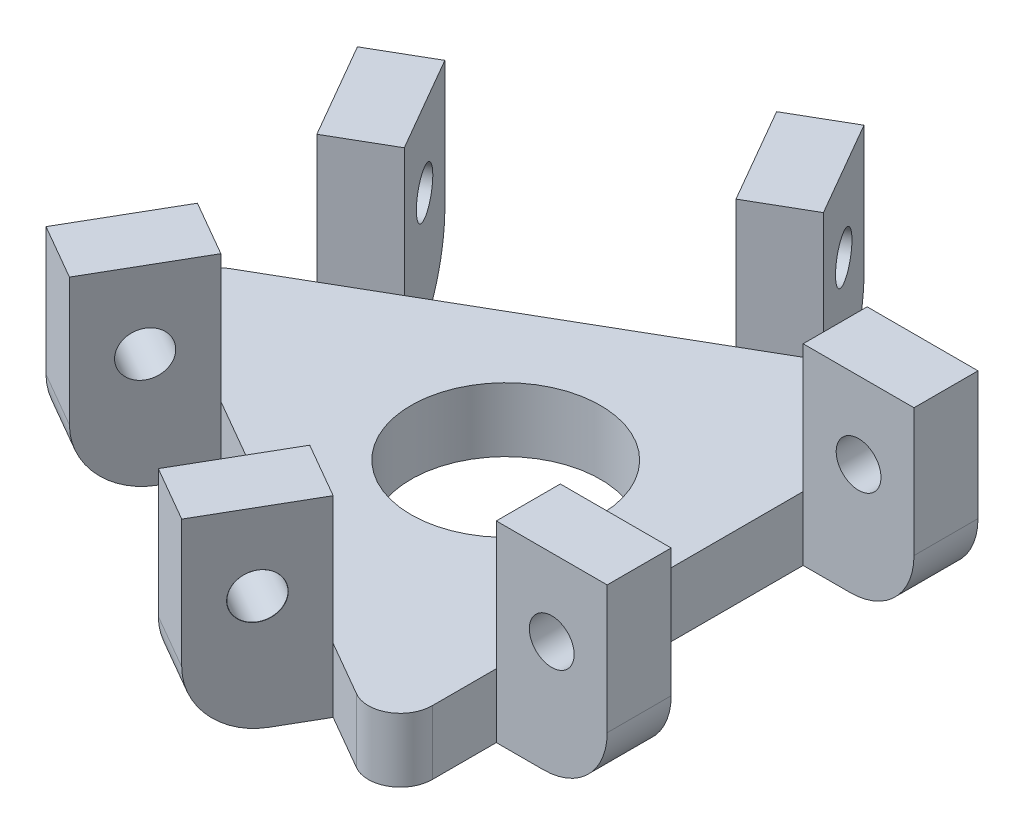
SolidWorks part; units mm, degrees
material "PLA"
ref_plane "Front" through (0, 0, 0) normal (0, 0, 1) x (1, 0, 0)
ref_plane "Top" through (0, 0, 0) normal (0, 1, 0) x (1, 0, 0)
ref_plane "Right" through (0, 0, 0) normal (1, 0, 0) x (0, 0, -1)
sketch "Sketch2" plane through (0, 0, 0) normal (0, 1, 0) x (0, 0, -1)
  line L0 (0, 0) -> (0, 50) construction
  line L1 (0, 0) -> (-43.3013, -25) construction
  line L2 (-43.3013, -20) -> (-38.3013, -11.3397)
  line L3 (4.3301, 47.5) -> (9.3301, 38.8397)
  line L4 (38.9711, -27.5) -> (28.9711, -27.5)
  line L5 (0, 0) -> (-23.8157, 13.75) construction
  line L9 (-38.3013, -11.3397) -> (-53.3013, -2.6795)
  line L10 (-33.3013, -2.6795) -> (-48.3013, 5.9808)
  line L11 (-53.3013, -2.6795) -> (-48.3013, 5.9808)
  line L12 (-14.3301, 30.1795) -> (-29.3301, 38.8397)
  line L13 (-24.3301, 47.5) -> (-29.3301, 38.8397)
  line L14 (-9.3301, 38.8397) -> (-24.3301, 47.5)
  line L17 (9.3301, 38.8397) -> (24.3301, 47.5)
  line L18 (24.3301, 47.5) -> (29.3301, 38.8397)
  line L19 (14.3301, 30.1795) -> (29.3301, 38.8397)
  line L20 (33.3013, -2.6795) -> (48.3013, 5.9808)
  line L21 (53.3013, -2.6795) -> (48.3013, 5.9808)
  line L22 (38.3013, -11.3397) -> (53.3013, -2.6795)
  line L25 (28.9711, -27.5) -> (28.9711, -44.8205)
  line L26 (28.9711, -44.8205) -> (18.9711, -44.8205)
  line L27 (18.9711, -27.5) -> (18.9711, -44.8205)
  line L28 (-28.9711, -27.5) -> (-28.9711, -44.8205)
  line L29 (-28.9711, -44.8205) -> (-18.9711, -44.8205)
  line L30 (-18.9711, -27.5) -> (-18.9711, -44.8205)
  line L32 (-33.3013, -2.6795) -> (-14.3301, 30.1795)
  line L33 (-9.3301, 38.8397) -> (-4.3301, 47.5)
  line L34 (14.3301, 30.1795) -> (33.3013, -2.6795)
  line L35 (38.3013, -11.3397) -> (43.3013, -20)
  line L36 (18.9711, -27.5) -> (-18.9711, -27.5)
  line L37 (-28.9711, -27.5) -> (-38.9711, -27.5)
  line L38 (-38.3013, -11.3397) -> (-33.3013, -2.6795)
  line L39 (-9.3301, 38.8397) -> (-14.3301, 30.1795)
  line L40 (9.3301, 38.8397) -> (14.3301, 30.1795)
  line L41 (38.3013, -11.3397) -> (33.3013, -2.6795)
  line L42 (28.9711, -27.5) -> (18.9711, -27.5)
  line L43 (-28.9711, -27.5) -> (-18.9711, -27.5)
  arc A0 (-43.3013, -20) -> (-38.9711, -27.5) centre (-38.9711, -22.5) ccw
  arc A1 (43.3013, -20) -> (38.9711, -27.5) centre (38.9711, -22.5) cw
  arc A2 (4.3301, 47.5) -> (-4.3301, 47.5) centre (0, 45) ccw
  circle A3 centre (-38.9711, -22.5) radius 5 construction
  circle A4 centre (0, 0) radius 14.7988
  dimension "D4" = 10
  dimension "D6" = 10
  dimension "D1" = 29.5977
  dimension "D3" = 50
  dimension "D7" = 10
  dimension "D8" = 15
extrude "Boss-Extrude1" add sketch "Sketch2" along normal blind 10 contours L3 A2 L33 L39 L32 L38 L2 A0 L37 L43 L36 L42 L4 A1 L35 L41 L34 L40 region at (16.256, 0, 39.7861)
extrude "Boss-Extrude3" add sketch "Sketch2<7>" along normal blind 30 contours L41 L22 L21 L20 | L17 L40 L19 L18 region at (-38.8397, 0, -19.3301) region at (2.6795, 0, -43.3013)
sketch "Sketch2<7>" plane through (0, 0, 0) normal (0, 1, 0) x (0, 0, -1) same geometry as "Sketch2"
fillet "Fillet1" radius 10 2 edges at (-43.1699, 0, -26.8301) (-1.6506, 0, -50.8013)
sketch "Sketch10" plane through (-25.0897, 0, 14.4856) normal (-0.866, 0, 0.5) x (0.5, 0, 0.866)
  line L1 (-36.1603, 18) -> (-27.5, 18) construction
  line L2 (-44.8205, 18) -> (-36.1603, 18) construction
  line L6 (-44.8205, 30) -> (-44.8205, 10) construction
  line L7 (-27.5, 30) -> (-27.5, 10) construction
  line L8 (-27.5, 30) -> (-44.8205, 30) construction
  point P0 (-36.1603, 18)
  dimension "D1" = 180
  dimension "D2" = 12
hole_wizard "Tap Drill for M8x1.0 Tap1" positions "Sketch10" profile "Sketch11" hole size "M8x1.0" standard "ISO" end condition through all
sketch "Sketch11" plane through (-43.1699, 18, -16.8301) normal (0, 1, 0) x (0.5, 0, 0.866)
  line L0 (0, 0) -> (0, 79.4375)
  line L1 (0, 79.4375) -> (3.5, 79.4375)
  line L2 (3.5, 79.4375) -> (3.5, 0.025)
  line L3 (3.5, 0.025) -> (3.525, 0)
  line L5 (3.525, 0) -> (0, 0)
  line L6 (-3.5, 0.025) -> (-3.525, 0) construction
  line L11 (0, -6.35) -> (0, 107.95) construction
  dimension "Thru Hole Dia." = 7
  dimension "Thru Hole Depth" = 79.4375
  dimension "Near C'Sink Dia." = 7.05
  dimension "Near C'Sink Angle" = 90
pattern_circular "CirPattern1" count 3 over 360 about axis through (0, 10, 0) along (0, 1, 0) of "Tap Drill for M8x1.0 Tap1", "Boss-Extrude3", "Fillet1"
